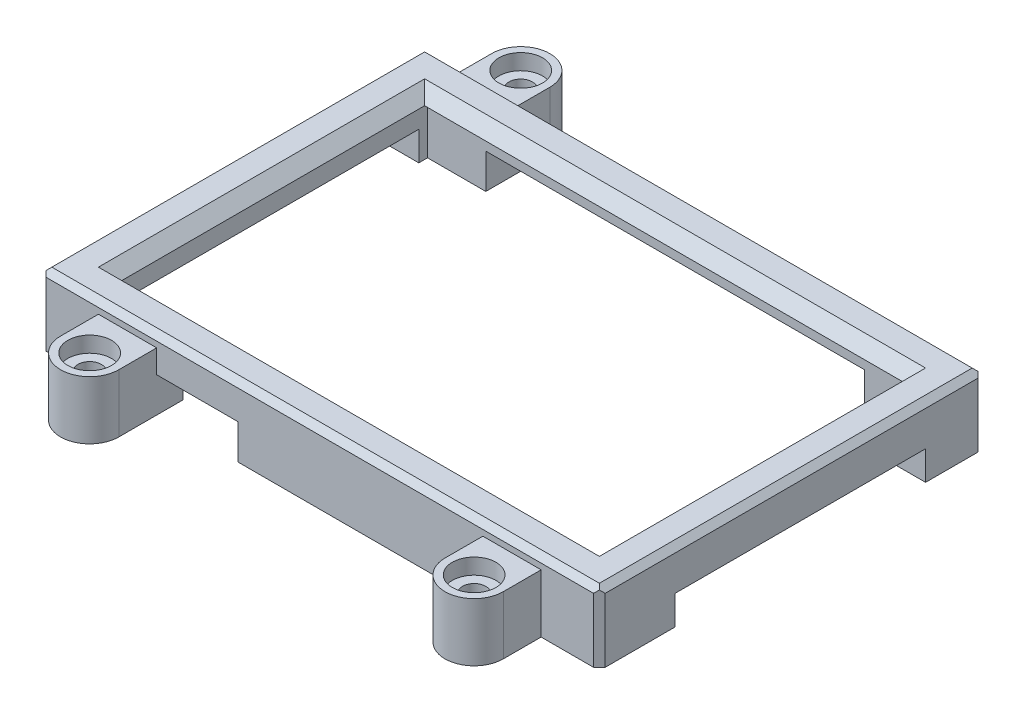
SolidWorks part; units mm, degrees
ref_plane "Front Plane" through (0, 0, 0) normal (0, 0, 1) x (1, 0, 0)
ref_plane "Top Plane" through (0, 0, 0) normal (0, 1, 0) x (1, 0, 0)
ref_plane "Right Plane" through (0, 0, 0) normal (1, 0, 0) x (0, 0, -1)
sketch "Sketch1" plane through (0, 0, 0) normal (0, 1, 0) x (1, 0, 0)
  line L0 (-33, -33) -> (-33, -39.5) construction
  line L1 (48, 33) -> (-48, 33)
  line L2 (48, 33) -> (48, -33)
  line L3 (48, -33) -> (-48, -33)
  line L4 (-48, 33) -> (-48, -33)
  line L5 (48, 33) -> (-48, -33) construction
  line L6 (48, -33) -> (-48, 33) construction
  line L7 (43, 28.5) -> (-43, 28.5)
  line L8 (43, 28.5) -> (43, -28.5)
  line L9 (43, -28.5) -> (-43, -28.5)
  line L10 (-43, 28.5) -> (-43, -28.5)
  line L11 (43, 28.5) -> (-43, -28.5) construction
  line L12 (43, -28.5) -> (-43, 28.5) construction
  line L19 (0, 45.7682) -> (0, -68.4353) construction
  line L20 (74.6195, 0) -> (-81.2839, 0) construction
  line L21 (-28, -33) -> (-28, -39.5)
  line L24 (-38, -33) -> (-38, -39.5)
  line L27 (33, -33) -> (33, -39.5) construction
  line L30 (28, -33) -> (28, -39.5)
  line L31 (38, -33) -> (38, -39.5)
  line L32 (-38, 33) -> (-38, 39.5) construction
  line L33 (-43, 33) -> (-43, 39.5)
  line L34 (-33, 33) -> (-33, 39.5)
  arc A9 (-28, -33) -> (-38, -33) centre (-33, -33) ccw
  arc A10 (-38, -39.5) -> (-28, -39.5) centre (-33, -39.5) ccw
  arc A11 (28, -33) -> (38, -33) centre (33, -33) cw
  arc A12 (38, -39.5) -> (28, -39.5) centre (33, -39.5) cw
  arc A13 (-43, 33) -> (-33, 33) centre (-38, 33) ccw
  arc A14 (-33, 39.5) -> (-43, 39.5) centre (-38, 39.5) ccw
  point P0 (0, 0)
  point P6 (0, 0)
  point P13 (-33, -36.25)
  point P24 (33, -36.25)
  point P31 (-38, 36.25)
  dimension "D5" = 6.5
  dimension "D6" = 5
  dimension "D9" = 5
  dimension "D1" = 66
  dimension "D2" = 96
  dimension "D3" = 57
  dimension "D4" = 86
  dimension "D7" = 15
  dimension "D8" = 6.5
  dimension "D10" = 10
extrude "Boss-Extrude1" add sketch "Sketch1" along normal blind 10
sketch "Sketch2" plane through (0, 10, 0) normal (0, 1, 0) x (1, 0, 0)
  line L0 (-43, 39.5) -> (-33, 39.5) construction
  line L1 (-38, -39.5) -> (-28, -39.5) construction
  line L2 (28, -39.5) -> (38, -39.5) construction
  circle A0 centre (-38, 39.5) radius 2
  circle A1 centre (33, -39.5) radius 2
  circle A2 centre (-33, -39.5) radius 2
  dimension "D1" = 4
  dimension "D2" = 4
extrude "Cut-Extrude1" cut sketch "Sketch2" against normal through all
sketch "Sketch4" plane through (0, 10, 0) normal (0, 1, 0) x (1, 0, 0)
  line L1 (48, 33) -> (-48, 33)
  line L2 (48, 33) -> (48, -33)
  line L3 (48, -33) -> (-48, -33)
  line L4 (-48, 33) -> (-48, -33)
  line L5 (48, 33) -> (-48, -33) construction
  line L6 (48, -33) -> (-48, 33) construction
  line L7 (41, 26) -> (-41, 26)
  line L8 (41, 26) -> (41, -26)
  line L9 (41, -26) -> (-41, -26)
  line L10 (-41, 26) -> (-41, -26)
  line L11 (41, 26) -> (-41, -26) construction
  line L12 (41, -26) -> (-41, 26) construction
  point P0 (0, 0)
  point P7 (0, 0)
  dimension "D1" = 52
  dimension "D2" = 82
extrude "Boss-Extrude2" add sketch "Sketch4" along normal blind 2
sketch "Sketch6" plane through (-48, 0, 0) normal (-1, 0, 0) x (0, 0, 1)
  line L6 (-33, 0) -> (33, 0) construction
  line L7 (-27, 0) -> (27, 0)
  line L8 (-27, 0) -> (-27, 5)
  line L9 (-27, 5) -> (27, 5)
  line L10 (27, 0) -> (27, 5)
  line L11 (-33, 10) -> (-33, 0) construction
  line L12 (33, 10) -> (33, 0) construction
  dimension "D1" = 5
  dimension "D2" = 6
  dimension "D3" = 6
extrude "Cut-Extrude2" cut sketch "Sketch6" against normal up to surface (5 mm away) up to face at (-43, 5, 0)
sketch "Sketch7" plane through (48, 0, 0) normal (1, 0, 0) x (0, 0, -1)
  line L5 (33, 0) -> (-33, 0) construction
  line L6 (-20, 0) -> (23, 0)
  line L7 (-20, 0) -> (-20, 5)
  line L8 (-20, 5) -> (23, 5)
  line L9 (23, 0) -> (23, 5)
  line L10 (-33, 10) -> (-33, 0) construction
  line L11 (33, 12) -> (33, 0) construction
  dimension "D1" = 5
  dimension "D2" = 13
  dimension "D3" = 10
extrude "Cut-Extrude3" cut sketch "Sketch7" against normal up to surface (5 mm away) up to face at (43, 5, 0)
chamfer "Chamfer1" distance 2 distance2 2 4 edges at (-41, 12, 0) (0, 12, 26) (41, 12, 0) (0, 12, -26)
chamfer "Chamfer2" distance 1 angle 45 4 edges at (0, 12, 33) (48, 12, 0) (0, 12, -33) (-48, 12, 0)
chamfer "Chamfer3" distance 1 angle 45 1 edges at (-48, 5.5, -33)
chamfer "Chamfer4" distance 1 angle 45 3 edges at (48, 5.5, -33) (48, 5.5, 33) (-48, 5.5, 33)
sketch "Sketch9" plane through (0, 10, 0) normal (0, 1, 0) x (1, 0, 0)
  circle A0 centre (-38, 39.5) radius 3.75
  circle A1 centre (-33, -39.5) radius 3.75
  circle A2 centre (33, -39.5) radius 3.75
  dimension "D1" = 7.5
  dimension "D2" = 7.5
  dimension "D3" = 7.5
extrude "Cut-Extrude4" cut sketch "Sketch9" against normal blind 2.7
sketch "Sketch10" plane through (0, 0, -33) normal (0, 0, -1) x (-1, 0, 0)
  line L0 (-47, 11) -> (-47, 0) construction
  line L1 (33, 0) -> (-32, 0)
  line L2 (33, 0) -> (33, 6)
  line L3 (33, 6) -> (-32, 6)
  line L4 (-32, 0) -> (-32, 6)
  dimension "D1" = 6
  dimension "D2" = 15
extrude "Cut-Extrude5" cut sketch "Sketch10" against normal up to surface (4.5 mm away) up to face at (0, 5, -28.5)
sketch "Sketch11" plane through (0, 0, 33) normal (0, 0, 1) x (1, 0, 0)
  line L1 (-28, 0) -> (-14, 0)
  line L2 (-28, 0) -> (-28, 6)
  line L3 (-28, 6) -> (-14, 6)
  line L4 (-14, 0) -> (-14, 6)
  dimension "D1" = 14
  dimension "D2" = 6
extrude "Cut-Extrude6" cut sketch "Sketch11" against normal up to surface (4.5 mm away) up to face at (0, 5, 28.5)
